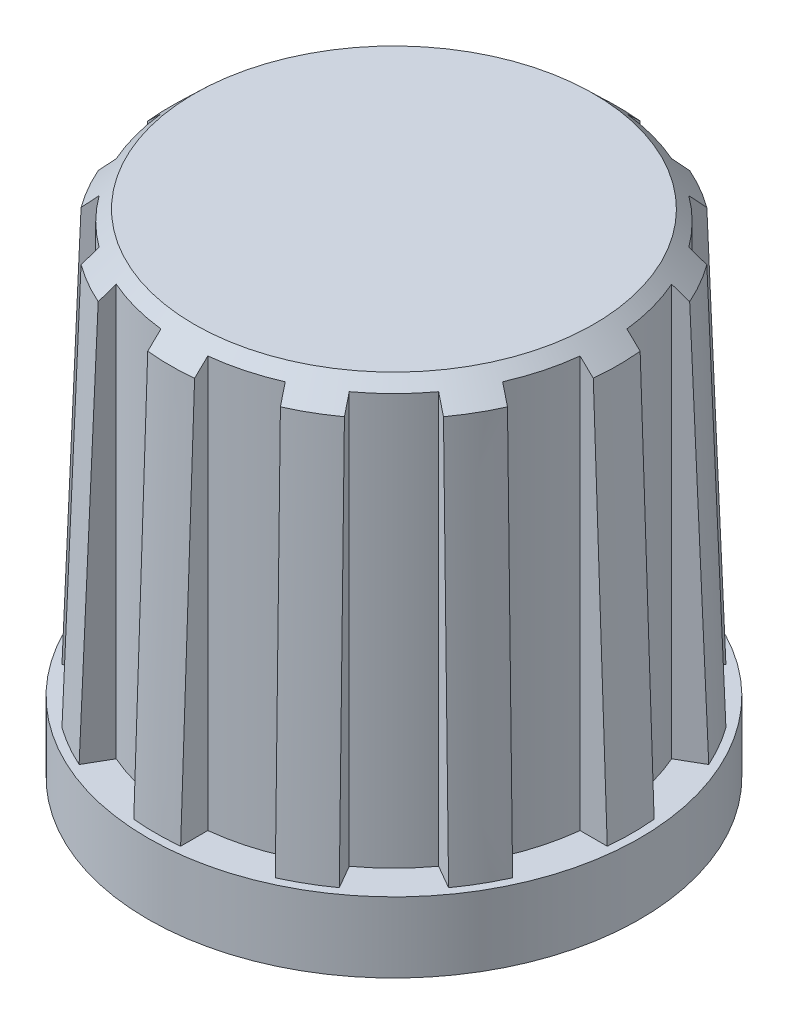
SolidWorks part; units mm, degrees
ref_plane "前视基准面" through (0, 0, 0) normal (0, 0, 1) x (1, 0, 0)
ref_plane "上视基准面" through (0, 0, 0) normal (0, 1, 0) x (1, 0, 0)
ref_plane "右视基准面" through (0, 0, 0) normal (1, 0, 0) x (0, 0, -1)
sketch "草图1" plane through (0, 0, 0) normal (0, 0, 1) x (1, 0, 0)
  line L0 (0, 35) -> (14.2088, 35)
  line L1 (14.2088, 35) -> (15.9336, 33.3343)
  line L2 (15.9336, 33.3343) -> (16.9231, 5)
  line L3 (16.9231, 5) -> (17.5, 5)
  line L4 (17.5, 5) -> (17.5, 0)
  line L5 (17.5, 0) -> (8, 0)
  line L6 (8, 0) -> (6.9175, 1.0825)
  line L7 (6.9175, 1.0825) -> (6.9175, 23.5)
  line L8 (6.9175, 23.5) -> (0, 23.5)
  line L9 (0, 23.5) -> (0, 35)
  line L10 (0, 0) -> (0, 35) construction
revolve "旋转1" add sketch "草图1" angle 360 about L10 reverse direction yes
cosmetic thread "装饰螺纹线1" parameters "D1"=23.5, "D2"=16
ref_plane "基准面4" through (0, 35, 0) normal (0, 1, 0) x (1, 0, 0)
sketch "草图2" plane through (0, 35, 0) normal (0, 1, 0) x (1, 0, 0)
  line L0 (-17.4205, -1.6667) -> (-14.9071, -1.6667)
  line L1 (-13.7433, -6.0102) -> (-15.9199, -7.2669)
  line L2 (-14.2532, -10.1536) -> (-12.0766, -8.8969)
  line L3 (-8.8969, -12.0766) -> (-10.1536, -14.2532)
  line L4 (-7.2669, -15.9199) -> (-6.0102, -13.7433)
  line L5 (-1.6667, -14.9071) -> (-1.6667, -17.4205)
  line L6 (1.6667, -17.4205) -> (1.6667, -14.9071)
  line L7 (6.0102, -13.7433) -> (7.2669, -15.9199)
  line L8 (10.1536, -14.2532) -> (8.8969, -12.0766)
  line L9 (12.0766, -8.8969) -> (14.2532, -10.1536)
  line L10 (15.9199, -7.2669) -> (13.7433, -6.0102)
  line L11 (14.9071, -1.6667) -> (17.4205, -1.6667)
  line L12 (17.4205, 1.6667) -> (14.9071, 1.6667)
  line L13 (13.7433, 6.0102) -> (15.9199, 7.2669)
  line L14 (14.2532, 10.1536) -> (12.0766, 8.8969)
  line L15 (8.8969, 12.0766) -> (10.1536, 14.2532)
  line L16 (7.2669, 15.9199) -> (6.0102, 13.7433)
  line L17 (1.6667, 14.9071) -> (1.6667, 17.4205)
  line L18 (-1.6667, 17.4205) -> (-1.6667, 14.9071)
  line L19 (-6.0102, 13.7433) -> (-7.2669, 15.9199)
  line L20 (-10.1536, 14.2532) -> (-8.8969, 12.0766)
  line L21 (-12.0766, 8.8969) -> (-14.2532, 10.1536)
  line L22 (-15.9199, 7.2669) -> (-13.7433, 6.0102)
  line L23 (-14.9071, 1.6667) -> (-17.4205, 1.6667)
  circle A0 centre (0, 0) radius 23.3333
  arc A1 (-17.4205, 1.6667) -> (-17.4205, -1.6667) centre (0, 0) ccw
  arc A2 (-14.9071, -1.6667) -> (-13.7433, -6.0102) centre (0, 0) ccw
  arc A3 (-15.9199, -7.2669) -> (-14.2532, -10.1536) centre (0, 0) ccw
  arc A4 (-12.0766, -8.8969) -> (-8.8969, -12.0766) centre (0, 0) ccw
  arc A5 (-10.1536, -14.2532) -> (-7.2669, -15.9199) centre (0, 0) ccw
  arc A6 (-6.0102, -13.7433) -> (-1.6667, -14.9071) centre (0, 0) ccw
  arc A7 (-1.6667, -17.4205) -> (1.6667, -17.4205) centre (0, 0) ccw
  arc A8 (1.6667, -14.9071) -> (6.0102, -13.7433) centre (0, 0) ccw
  arc A9 (7.2669, -15.9199) -> (10.1536, -14.2532) centre (0, 0) ccw
  arc A10 (8.8969, -12.0766) -> (12.0766, -8.8969) centre (0, 0) ccw
  arc A11 (14.2532, -10.1536) -> (15.9199, -7.2669) centre (0, 0) ccw
  arc A12 (13.7433, -6.0102) -> (14.9071, -1.6667) centre (0, 0) ccw
  arc A13 (17.4205, -1.6667) -> (17.4205, 1.6667) centre (0, 0) ccw
  arc A14 (14.9071, 1.6667) -> (13.7433, 6.0102) centre (0, 0) ccw
  arc A15 (15.9199, 7.2669) -> (14.2532, 10.1536) centre (0, 0) ccw
  arc A16 (12.0766, 8.8969) -> (8.8969, 12.0766) centre (0, 0) ccw
  arc A17 (10.1536, 14.2532) -> (7.2669, 15.9199) centre (0, 0) ccw
  arc A18 (6.0102, 13.7433) -> (1.6667, 14.9071) centre (0, 0) ccw
  arc A19 (1.6667, 17.4205) -> (-1.6667, 17.4205) centre (0, 0) ccw
  arc A20 (-1.6667, 14.9071) -> (-6.0102, 13.7433) centre (0, 0) ccw
  arc A21 (-7.2669, 15.9199) -> (-10.1536, 14.2532) centre (0, 0) ccw
  arc A22 (-8.8969, 12.0766) -> (-12.0766, 8.8969) centre (0, 0) ccw
  arc A23 (-14.2532, 10.1536) -> (-15.9199, 7.2669) centre (0, 0) ccw
  arc A24 (-13.7433, 6.0102) -> (-14.9071, 1.6667) centre (0, 0) ccw
extrude "切除-拉伸1" cut sketch "草图2" against normal blind 30
ref_plane "基准面5" through (0, 23.5, 0) normal (0, 1, 0) x (1, 0, 0)
sketch "草图3" plane through (0, 23.5, 0) normal (0, 1, 0) x (1, 0, 0)
  line L0 (1.5385, -2.7578) -> (1.5385, 2.7578)
  line L1 (-1.5385, 2.7578) -> (-1.5385, -2.7578)
  arc A0 (-1.5385, -2.7578) -> (1.5385, -2.7578) centre (0, 0) ccw
  arc A1 (1.5385, 2.7578) -> (-1.5385, 2.7578) centre (0, 0) ccw
extrude "切除-拉伸2" cut sketch "草图3" along normal blind 5
ref_plane "基准面6" through (0, 28.5, 0) normal (0, 1, 0) x (1, 0, 0)
ref_plane "handle_to_piston XY" through (0, 28.5, 0) normal (0, 1, 0) x (1, 0, 0)
ref_plane "handle_to_piston XZ" through (0, 0, 0) normal (0, 0, 1) x (1, 0, 0)
ref_plane "handle_to_piston YZ" through (0, 0, 0) normal (1, 0, 0) x (0, 0, -1)
ref_axis "handle_to_piston X" through (-80.9, 28.5, 0) along (1, 0, 0)
ref_axis "handle_to_piston Y" through (0, 28.5, 50) along (0, 0, -1)
ref_axis "handle_to_piston Z" through (0, 50, 0) along (0, -1, 0)
sketch3d "handle_to_piston"
  point P0 (0, 28.5, 0)
